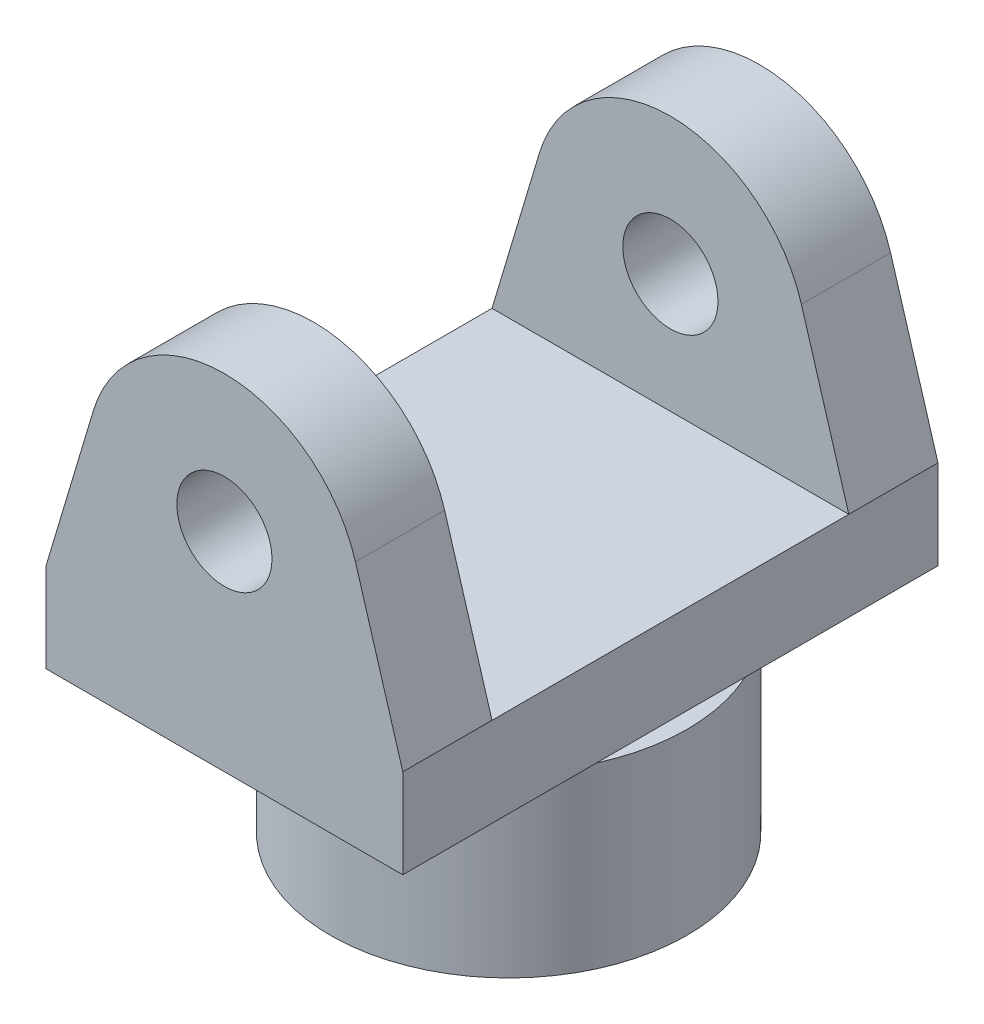
SolidWorks part; units mm, degrees
ref_plane "Front Plane" through (0, 0, 0) normal (0, 0, 1) x (1, 0, 0)
ref_plane "Top Plane" through (0, 0, 0) normal (0, 1, 0) x (1, 0, 0)
ref_plane "Right Plane" through (0, 0, 0) normal (1, 0, 0) x (0, 0, -1)
sketch "Sketch1" plane through (0, 0, 0) normal (0, 0, 1) x (1, 0, 0)
  line L0 (0, 0) -> (0, 14199.0957) construction
  line L1 (0, 0) -> (-14199.0957, 0) construction
  line L2 (-30, -20) -> (-22.0329, 6.5993)
  line L3 (-30, -35) -> (30, -35)
  line L4 (-30, -35) -> (-30, -20)
  line L5 (-30, -20) -> (30, -20)
  line L6 (30, -35) -> (30, -20)
  line L7 (-30, -35) -> (30, -20) construction
  line L8 (-30, -20) -> (30, -35) construction
  line L9 (30, -20) -> (22.0329, 6.5993)
  circle A0 centre (0, 0) radius 8
  arc A1 (22.0329, 6.5993) -> (-22.0329, 6.5993) centre (0, 0) ccw
  point P7 (0, 0)
  point P8 (0, -27.5)
  point P15 (-22.0329, 6.5993)
  point P16 (22.0329, 6.5993)
  point P17 (30, -20)
  dimension "D2" = 46
  dimension "D3" = 16
  dimension "D1" = 15
  dimension "D4" = 35
  dimension "D5" = 60
extrude "Boss-Extrude2" add sketch "Sketch1" along normal blind 15 contours L9 A1 L2 L5 A0 region at (-25.3093, -6.9121, 0)
extrude "Boss-Extrude3" add sketch "Sketch1<5>" along normal blind 90 contours L3 L6 L5 L4 region at (0, -27.5, 0)
sketch "Sketch1<5>" plane through (0, 0, 0) normal (0, 0, 1) x (1, 0, 0) same geometry as "Sketch1"
ref_plane "Plane1" through (0, 0, 90) normal (0, 0, 1) x (1, 0, 0)
sketch "Sketch2" plane through (0, 0, 90) normal (0, 0, 1) x (1, 0, 0)
  line L0 (-30, -20) -> (30, -20) construction
  line L1 (30, -35) -> (30, -20) construction
  line L2 (-30, -35) -> (30, -35) construction
  line L3 (-30, -35) -> (-30, -20) construction
  line L4 (-30, -20) -> (-22.0329, 6.5993) construction
  line L5 (30, -20) -> (22.0329, 6.5993) construction
  line L6 (-30, -20) -> (30, -20)
  line L7 (30, -35) -> (30, -20)
  line L8 (-30, -35) -> (30, -35)
  line L9 (-30, -35) -> (-30, -20)
  line L10 (-30, -20) -> (-22.0329, 6.5993)
  line L11 (30, -20) -> (22.0329, 6.5993)
  arc A0 (22.0329, 6.5993) -> (-22.0329, 6.5993) centre (0, 0) ccw construction
  circle A1 centre (0, 0) radius 8
  circle A2 centre (0, 0) radius 8
  arc A3 (22.0329, 6.5993) -> (-22.0329, 6.5993) centre (0, 0) ccw
  dimension "D1" = 0
extrude "Boss-Extrude4" add sketch "Sketch2" against normal blind 15 contours L11 A3 L10 L6 A2 region at (-25.3093, -6.9121, 90)
sketch "Sketch3" plane through (0, -35, 0) normal (0, -1, 0) x (1, 0, 0)
  line L2 (-2.2791, 58.5618) -> (-2.2791, 64.4177)
  line L3 (-2.2791, 64.4177) -> (7.7209, 64.4177)
  line L4 (7.7209, 58.5618) -> (7.7209, 64.4177)
  circle A0 centre (2.7209, 44.9177) radius 30
  arc A1 (-2.2791, 58.5618) -> (7.7209, 58.5618) centre (2.7209, 44.9177) ccw
  dimension "D1" = 60
  dimension "D2" = 45
  dimension "D3" = 10
extrude "Boss-Extrude5" add sketch "Sketch3" along normal blind 30
